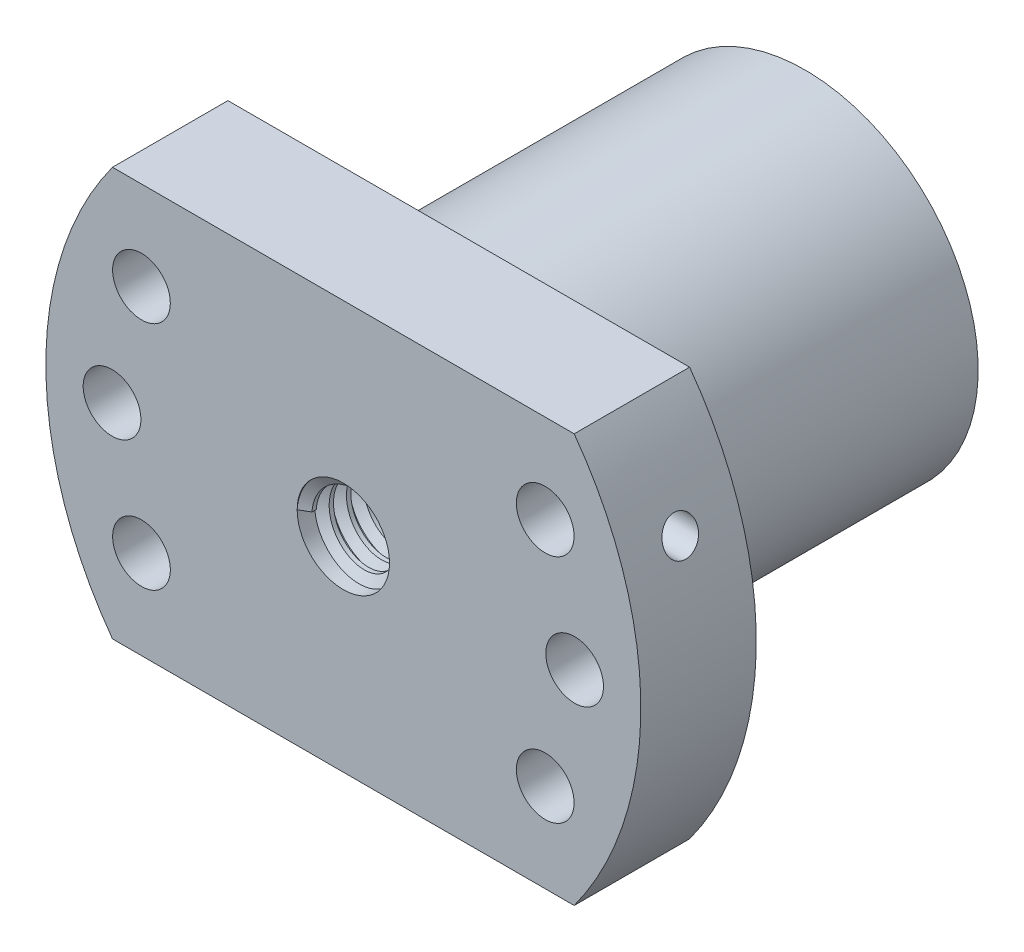
SolidWorks part; units mm, degrees
material "Cast Alloy Steel"
ref_plane "Front Plane" through (0, 0, 0) normal (0, 0, 1) x (1, 0, 0)
ref_plane "Top Plane" through (0, 0, 0) normal (0, 1, 0) x (1, 0, 0)
ref_plane "Right Plane" through (0, 0, 0) normal (1, 0, 0) x (0, 0, -1)
sketch "Sketch1" plane through (0, 0, 0) normal (0, 0, 1) x (1, 0, 0)
  line L1 (-20, -17.6953) -> (20, -17.6953)
  line L3 (-20, 17.6953) -> (20, 17.6953)
  line L5 (-20, -17.6953) -> (20, 17.6953) construction
  line L6 (-20, 17.6953) -> (20, -17.6953) construction
  arc A0 (-20, 17.6953) -> (-20, -17.6953) centre (4.2255, 0) ccw
  arc A1 (20, 17.6953) -> (20, -17.6953) centre (-4.2255, 0) cw
  point P0 (0, 0)
  dimension "D2" = 30
  dimension "D3" = 30
  dimension "D1" = 40
extrude "Boss-Extrude1" add sketch "Sketch1" against normal blind 10
sketch "Sketch2" plane through (0, 0, -10) normal (0, 0, -1) x (-1, 0, 0)
  circle A0 centre (0, 0) radius 15
  dimension "D1" = 30
extrude "Boss-Extrude2" add sketch "Sketch2" along normal blind 30
sketch "Sketch3" plane through (0, 0, 0) normal (0, 0, 1) x (1, 0, 0)
  circle A0 centre (0, 0) radius 4
  dimension "D1" = 8
extrude "Cut-Extrude1" cut sketch "Sketch3" against normal through all
thread "Thread1" pitch 1.5 method extrude profile "Thread Profile1" start angle 0, offset 0, length 38, pitch 1.5, diameter 8
ref_plane "Plane1" through (-4, 0, 0) normal (0, -1, 0) x (-1, 0, 0)
sketch "Thread Profile1" plane through (-4, 0, 0) normal (0, -1, 0) x (-1, 0, 0)
  line L0 (0, 0) -> (0, 1.5) construction
  line L11 (0, 0) -> (0, 1.3125)
  line L12 (0, 1.3125) -> (-0.8119, 0.8437)
  line L13 (-0.8119, 0.8437) -> (-0.8119, 0.4687)
  line L15 (-0.8119, 0.4687) -> (0, 0)
  line L17 (-0.8119, 0.6562) -> (0, 0.6562) construction
  point P2 (0, 0)
  dimension "Pitch" = 1.5
  dimension "Profile_Angle" = 60
  dimension "Profile_Land" = 0.375
  dimension "Profile_Height" = 0.8119
sketch "Sketch6" plane through (0, 0, 0) normal (0, 0, 1) x (1, 0, 0)
  line L0 (0, 0) -> (0, 9.448) construction
  line L1 (0, 9.448) -> (0, 0) construction
  line L2 (0, 0) -> (9.3162, 0) construction
  circle A0 centre (-17.4898, 10) radius 2.5
  circle A1 centre (-20.0385, 0) radius 2.5
  circle A2 centre (20.0385, 0) radius 2.5
  circle A3 centre (17.4898, 10) radius 2.5
  circle A4 centre (17.4898, -10) radius 2.5
  circle A5 centre (-17.4898, -10) radius 2.5
  dimension "D1" = 5
  dimension "D2" = 5
  dimension "D3" = 10
  dimension "D4" = 10
extrude "Cut-Extrude2" cut sketch "Sketch6" against normal blind 20
sketch "Sketch7" plane through (0, 0, 0) normal (1, 0, 0) x (0, 0, -1)
  circle A0 centre (5, 9.6139) radius 1.5
  dimension "D1" = 3
extrude "Cut-Extrude3" cut sketch "Sketch7" against normal through all both and the other way through all
